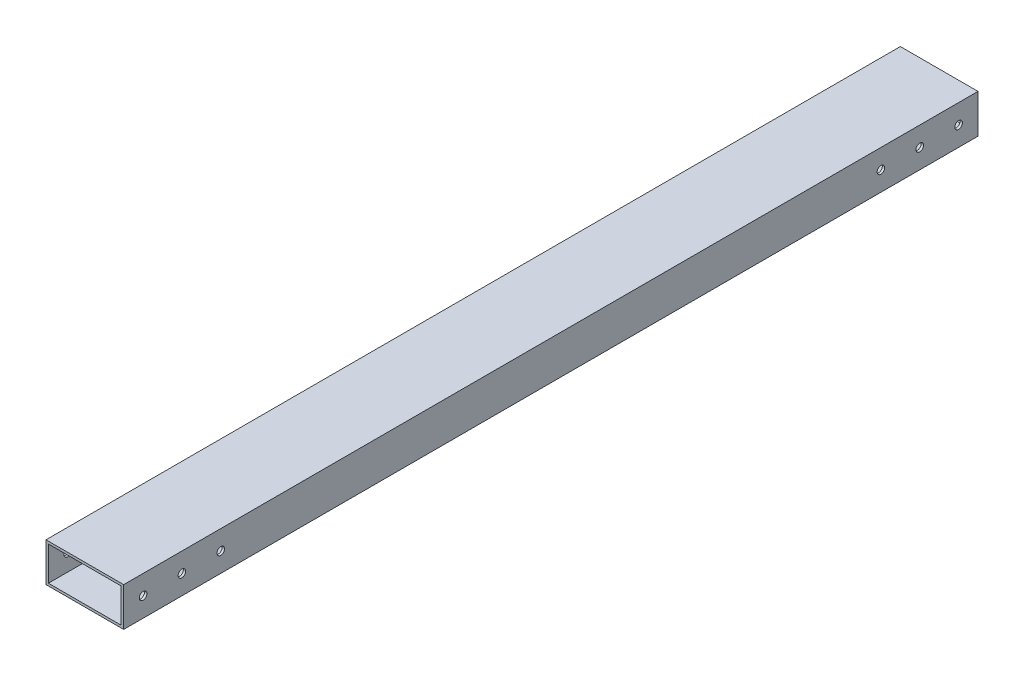
SolidWorks part; units mm, degrees
ref_plane "Front Plane" through (0, 0, 0) normal (0, 0, 1) x (1, 0, 0)
ref_plane "Top Plane" through (0, 0, 0) normal (0, 1, 0) x (1, 0, 0)
ref_plane "Right Plane" through (0, 0, 0) normal (1, 0, 0) x (0, 0, -1)
sketch "Sketch1" plane through (0, 0, 0) normal (0, 0, 1) x (1, 0, 0)
  line L1 (-25.4, -12.7) -> (25.4, -12.7)
  line L2 (-25.4, -12.7) -> (-25.4, 12.7)
  line L3 (-25.4, 12.7) -> (25.4, 12.7)
  line L4 (25.4, -12.7) -> (25.4, 12.7)
  line L5 (-25.4, -12.7) -> (25.4, 12.7) construction
  line L6 (-25.4, 12.7) -> (25.4, -12.7) construction
  point P0 (0, 0)
  dimension "D1" = 50.8
  dimension "D2" = 25.4
extrude "Boss-Extrude1" add sketch "Sketch1" along normal mid plane 558.8
shell "Shell1" thickness 1.5875 removed face at (0, 0, -279.4) removed face at (0, 0, 279.4)
sketch "Sketch3" plane through (0, 0, 0) normal (1, 0, 0) x (0, 0, -1)
  line L0 (-279.4, -12.7) -> (-279.4, 12.7) construction
  line L1 (0, 12.7) -> (0, -12.7) construction
  line L2 (-279.4, 12.7) -> (279.4, 12.7) construction
  line L3 (-279.4, -12.7) -> (279.4, -12.7) construction
  circle A0 centre (-266.7, 0) radius 2.4892
  circle A1 centre (-241.3, 0) radius 2.4892
  circle A2 centre (-215.9, 0) radius 2.4892
  circle A3 centre (215.9, 0) radius 2.4892
  circle A4 centre (241.3, 0) radius 2.4892
  circle A5 centre (266.7, 0) radius 2.4892
  point P4 (-279.4, 0)
  dimension "D2" = 4.9784
  dimension "D1" = 12.7
  dimension "D3" = 25.4
  dimension "D4" = 25.4
extrude "Cut-Extrude1" cut sketch "Sketch3" against normal through all both and the other way through all
equation "\"D4@Sketch3\"=\"D3@Sketch3\""
